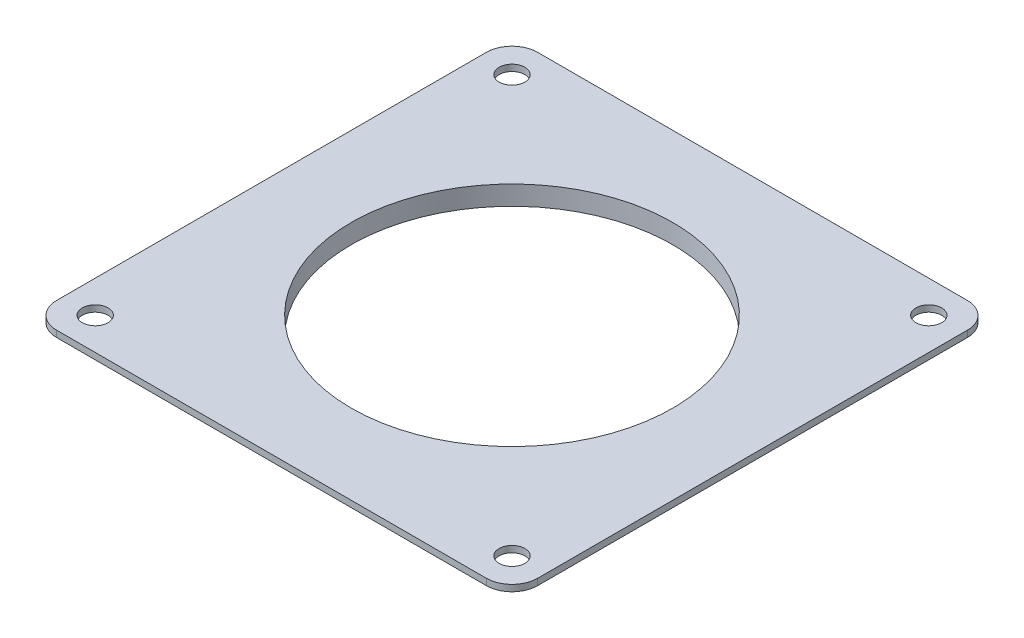
SolidWorks part; units mm, degrees
ref_plane "Front Plane" through (0, 0, 0) normal (0, 0, 1) x (1, 0, 0)
ref_plane "Top Plane" through (0, 0, 0) normal (0, 1, 0) x (1, 0, 0)
ref_plane "Right Plane" through (0, 0, 0) normal (1, 0, 0) x (0, 0, -1)
sketch "Sketch1" plane through (0, 0, 0) normal (0, 1, 0) x (1, 0, 0)
  line L1 (-42.418, -47.498) -> (42.418, -47.498)
  line L2 (-47.498, -42.418) -> (-47.498, 42.418)
  line L3 (-42.418, 47.498) -> (42.418, 47.498)
  line L4 (47.498, -42.418) -> (47.498, 42.418)
  line L5 (-47.498, -47.498) -> (47.498, 47.498) construction
  line L6 (-47.498, 47.498) -> (47.498, -47.498) construction
  arc A0 (-42.418, -47.498) -> (-47.498, -42.418) centre (-42.418, -42.418) cw
  arc A1 (42.418, -47.498) -> (47.498, -42.418) centre (42.418, -42.418) ccw
  arc A2 (42.418, 47.498) -> (47.498, 42.418) centre (42.418, 42.418) cw
  arc A3 (-47.498, 42.418) -> (-42.418, 47.498) centre (-42.418, 42.418) cw
  point P0 (0, 0)
  dimension "D3" = 5.08
  dimension "D1" = 94.996
  dimension "D2" = 94.996
extrude "Boss-Extrude1" add sketch "Sketch1" along normal blind 1.27
sketch "Sketch2" plane through (0, 0, 0) normal (0, -1, 0) x (1, 0, 0)
  circle A0 centre (0, 0) radius 38.1
  dimension "D1" = 76.2
extrude "Boss-Extrude2" add sketch "Sketch2" along normal blind 2.54
fillet "Fillet1" radius 10.16 1 edges at (0, 0, -38.1)
sketch "Sketch3" plane through (0, 1.27, 0) normal (0, 1, 0) x (1, 0, 0)
  circle A0 centre (0, 0) radius 31.75
  dimension "D1" = 63.5
extrude "Cut-Extrude1" cut sketch "Sketch3" against normal through all
sketch "Sketch4" plane through (0, 1.27, 0) normal (0, 1, 0) x (1, 0, 0)
  line L0 (-61.4593, 0) -> (61.4593, 0) construction
  line L1 (0, -51.5197) -> (0, 51.5197) construction
  line L2 (42.418, 47.498) -> (-42.418, 47.498) construction
  line L3 (-47.498, 42.418) -> (-47.498, -42.418) construction
  circle A0 centre (-41.148, 41.148) radius 2.54
  circle A2 centre (41.148, 41.148) radius 2.54
  circle A3 centre (-41.148, -41.148) radius 2.54
  circle A4 centre (41.148, -41.148) radius 2.54
  point P5 (0, 0)
  point P9 (0, 0)
  point P14 (-40.8253, 40.8253)
  dimension "D1" = 5.08
  dimension "D2" = 6.35
  dimension "D3" = 6.35
extrude "Cut-Extrude2" cut sketch "Sketch4" against normal through all
